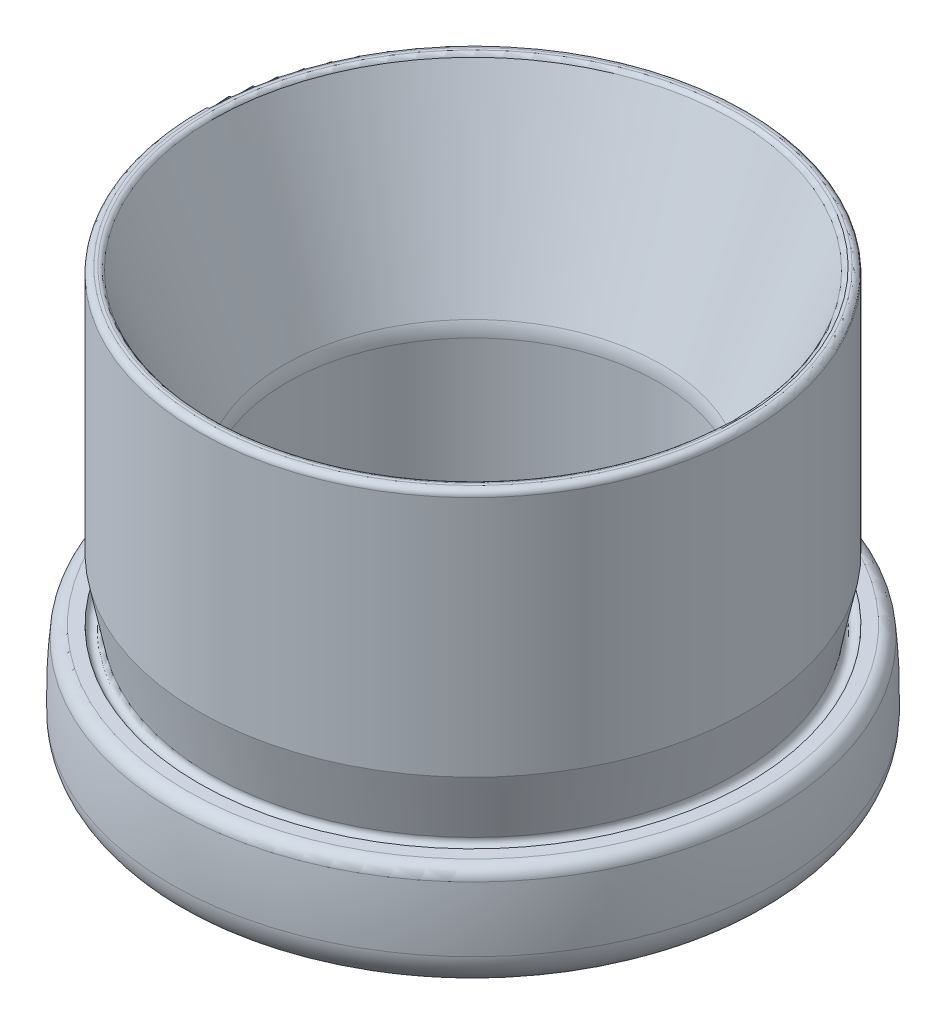
SolidWorks part; units mm, degrees
material "ABS"
ref_plane "Płaszczyzna przednia" through (0, 0, 0) normal (0, 0, 1) x (1, 0, 0)
ref_plane "Płaszczyzna górna" through (0, 0, 0) normal (0, 1, 0) x (1, 0, 0)
ref_plane "Płaszczyzna prawa" through (0, 0, 0) normal (1, 0, 0) x (0, 0, -1)
sketch "Szkic1" plane through (0, 0, 0) normal (0, 0, 1) x (1, 0, 0)
  line L0 (11.2358, 39.5413) -> (11.2358, 20.0413)
  line L1 (11.2358, 20.0413) -> (12.2259, 15.1403)
  line L2 (11.2358, 15.0413) -> (10.2322, 15.0413)
  line L3 (18.3358, 11.5573) -> (18.3358, 24.4546)
  line L4 (11.7358, 40.0413) -> (11.9666, 40.0413)
  line L5 (12.3372, 39.792) -> (18.1148, 25.5848)
  line L6 (13.8259, 6.7185) -> (17.1153, 9.1421)
  line L15 (33.3358, 21.0413) -> (33.3358, 66.3731) construction
  arc A0 (9.237, 14.1393) -> (9.0472, 9.0636) centre (50.8524, 10.0413) ccw
  arc A1 (11.2358, 15.0413) -> (12.2259, 15.1403) centre (11.7358, 15.0413) ccw
  arc A2 (10.2322, 15.0413) -> (9.237, 14.1393) centre (10.2322, 14.0413) ccw
  arc A3 (11.7358, 40.0413) -> (11.2358, 39.5413) centre (11.7358, 39.5413) ccw
  arc A4 (9.0472, 9.0636) -> (13.8259, 6.7185) centre (12.0464, 9.1337) ccw
  arc A5 (17.1153, 9.1421) -> (18.3358, 11.5573) centre (15.3358, 11.5573) ccw
  arc A6 (18.3358, 24.4546) -> (18.1148, 25.5848) centre (15.3358, 24.4546) ccw
  arc A7 (12.3372, 39.792) -> (11.9666, 40.0413) centre (11.9666, 39.6413) ccw
revolve "Obrót1" add sketch "Szkic1" angle 360 about L15
